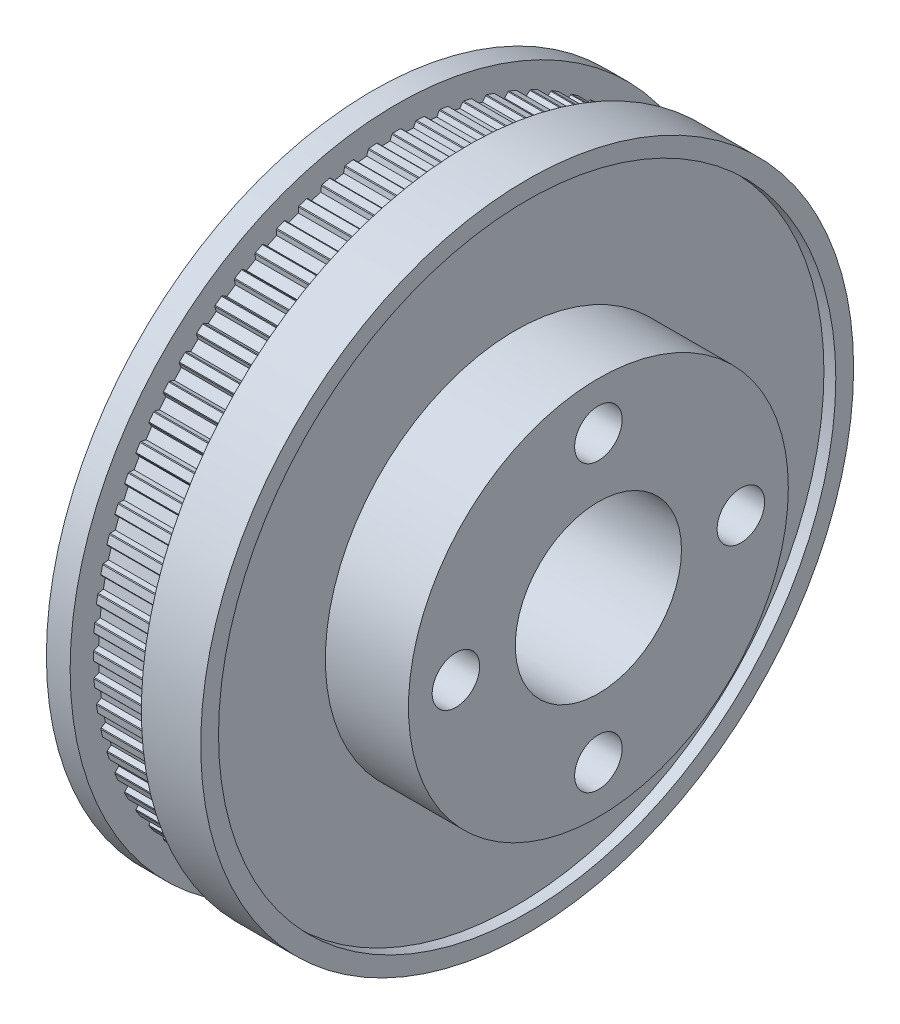
SolidWorks part; units mm, degrees
other "Câmera1"
ref_plane "Plano frontal" through (0, 0, 0) normal (0, 0, 1) x (1, 0, 0)
ref_plane "Plano superior" through (0, 0, 0) normal (0, 1, 0) x (1, 0, 0)
ref_plane "Plano direito" through (0, 0, 0) normal (1, 0, 0) x (0, 0, -1)
sketch "Esboço2" plane through (0, 0, 0) normal (1, 0, 0) x (0, 0, -1)
  line L0 (-0.3275, 25.545) -> (0.3325, 25.545)
  line L1 (-0.3949, 25.4981) -> (-0.5455, 25.0931)
  line L2 (0.3999, 25.4981) -> (0.5509, 25.0915)
  line L3 (1.6069, 25.4505) -> (1.425, 25.0585)
  line L4 (-0.3275, 25.545) -> (-0.3949, 25.4981)
  line L5 (1.425, 25.0585) -> (0.5509, 25.0915)
  line L6 (0.3325, 25.545) -> (0.3999, 25.4981)
  line L7 (1.6777, 25.4919) -> (1.6069, 25.4505)
  line L8 (1.6777, 25.4919) -> (2.3357, 25.4402)
  line L9 (2.3357, 25.4402) -> (2.3992, 25.3882)
  line L10 (2.3992, 25.3882) -> (2.5178, 24.9709)
  line L11 (3.3867, 24.8695) -> (2.5178, 24.9709)
  line L12 (3.5987, 25.246) -> (3.3867, 24.8695)
  line L13 (3.6727, 25.2817) -> (3.5987, 25.246)
  line L14 (3.6727, 25.2817) -> (4.3245, 25.1785)
  line L15 (4.3245, 25.1785) -> (4.3838, 25.1216)
  line L16 (4.3838, 25.1216) -> (4.4693, 24.6964)
  line L17 (5.3275, 24.5271) -> (4.4693, 24.6964)
  line L18 (5.5684, 24.8858) -> (5.3275, 24.5271)
  line L19 (5.6449, 24.9156) -> (5.5684, 24.8858)
  line L20 (5.6449, 24.9156) -> (6.2867, 24.7616)
  line L21 (6.2867, 24.7616) -> (6.3413, 24.7003)
  line L22 (6.3413, 24.7003) -> (6.3931, 24.2696)
  line L23 (7.2354, 24.0335) -> (6.3931, 24.2696)
  line L24 (7.5038, 24.3722) -> (7.2354, 24.0335)
  line L25 (7.5824, 24.3959) -> (7.5038, 24.3722)
  line L26 (7.5824, 24.3959) -> (8.2101, 24.192)
  line L27 (8.2101, 24.192) -> (8.2597, 24.1266)
  line L28 (8.2597, 24.1266) -> (8.2776, 23.6932)
  line L29 (9.0988, 23.3917) -> (8.2776, 23.6932)
  line L30 (9.3929, 23.7083) -> (9.0988, 23.3917)
  line L31 (9.4731, 23.7258) -> (9.3929, 23.7083)
  line L32 (9.4731, 23.7258) -> (10.0828, 23.4733)
  line L33 (10.0828, 23.4733) -> (10.1272, 23.4042)
  line L34 (10.1272, 23.4042) -> (10.111, 22.9707)
  line L35 (10.906, 22.6057) -> (10.111, 22.9707)
  line L36 (11.224, 22.8983) -> (10.906, 22.6057)
  line L37 (11.3054, 22.9094) -> (11.224, 22.8983)
  line L38 (11.3054, 22.9094) -> (11.8934, 22.6098)
  line L39 (11.8934, 22.6098) -> (11.9322, 22.5374)
  line L40 (11.9322, 22.5374) -> (11.8821, 22.1066)
  line L41 (12.646, 21.6804) -> (11.8821, 22.1066)
  line L42 (12.986, 21.9471) -> (12.646, 21.6804)
  line L43 (13.068, 21.9518) -> (12.986, 21.9471)
  line L44 (13.068, 21.9518) -> (13.6307, 21.607)
  line L45 (13.6307, 21.607) -> (13.6637, 21.5318)
  line L46 (13.6637, 21.5318) -> (13.58, 21.1062)
  line L47 (14.3081, 20.6213) -> (13.58, 21.1062)
  line L48 (14.6679, 20.8605) -> (14.3081, 20.6213)
  line L49 (14.75, 20.8588) -> (14.6679, 20.8605)
  line L50 (14.75, 20.8588) -> (15.284, 20.4709)
  line L51 (15.284, 20.4709) -> (15.311, 20.3934)
  line L52 (15.311, 20.3934) -> (15.1941, 19.9756)
  line L53 (15.8819, 19.4352) -> (15.1941, 19.9756)
  line L54 (16.2594, 19.6454) -> (15.8819, 19.4352)
  line L55 (16.3411, 19.6373) -> (16.2594, 19.6454)
  line L56 (16.3411, 19.6373) -> (16.843, 19.2086)
  line L57 (16.843, 19.2086) -> (16.8638, 19.1292)
  line L58 (16.8638, 19.1292) -> (16.7145, 18.722)
  line L59 (17.3578, 18.1292) -> (16.7145, 18.722)
  line L60 (17.7507, 18.3092) -> (17.3578, 18.1292)
  line L61 (17.8315, 18.2946) -> (17.7507, 18.3092)
  line L62 (17.8315, 18.2946) -> (18.2982, 17.8279)
  line L63 (18.2982, 17.8279) -> (18.3127, 17.7471)
  line L64 (18.3127, 17.7471) -> (18.1319, 17.3528)
  line L65 (18.7267, 16.7114) -> (18.1319, 17.3528)
  line L66 (19.1325, 16.86) -> (18.7267, 16.7114)
  line L67 (19.2119, 16.8392) -> (19.1325, 16.86)
  line L68 (19.2119, 16.8392) -> (19.6405, 16.3373)
  line L69 (19.6405, 16.3373) -> (19.6487, 16.2556)
  line L70 (19.6487, 16.2556) -> (19.4375, 15.8767)
  line L71 (19.9801, 15.1906) -> (19.4375, 15.8767)
  line L72 (20.3963, 15.3069) -> (19.9801, 15.1906)
  line L73 (20.4738, 15.2799) -> (20.3963, 15.3069)
  line L74 (20.4738, 15.2799) -> (20.8618, 14.746)
  line L75 (20.8618, 14.746) -> (20.8635, 14.6639)
  line L76 (20.8635, 14.6639) -> (20.6232, 14.3027)
  line L77 (21.1104, 13.5762) -> (20.6232, 14.3027)
  line L78 (21.5344, 13.6595) -> (21.1104, 13.5762)
  line L79 (21.6096, 13.6265) -> (21.5344, 13.6595)
  line L80 (21.6096, 13.6265) -> (21.9544, 13.0637)
  line L81 (21.9544, 13.0637) -> (21.9497, 12.9818)
  line L82 (21.9497, 12.9818) -> (21.6818, 12.6406)
  line L83 (22.1105, 11.878) -> (21.6818, 12.6406)
  line L84 (22.5397, 11.9278) -> (22.1105, 11.878)
  line L85 (22.6121, 11.889) -> (22.5397, 11.9278)
  line L86 (22.6121, 11.889) -> (22.9117, 11.3009)
  line L87 (22.9117, 11.3009) -> (22.9006, 11.2196)
  line L88 (22.9006, 11.2196) -> (22.6068, 10.9005)
  line L89 (22.9742, 10.1066) -> (22.6068, 10.9005)
  line L90 (23.4061, 10.1226) -> (22.9742, 10.1066)
  line L91 (23.4752, 10.0782) -> (23.4061, 10.1226)
  line L92 (23.4752, 10.0782) -> (23.7277, 9.4685)
  line L93 (23.7277, 9.4685) -> (23.7102, 9.3882)
  line L94 (23.7102, 9.3882) -> (23.3923, 9.0932)
  line L95 (23.6964, 8.2729) -> (23.3923, 9.0932)
  line L96 (24.1281, 8.2549) -> (23.6964, 8.2729)
  line L97 (24.1935, 8.2053) -> (24.1281, 8.2549)
  line L98 (24.1935, 8.2053) -> (24.3975, 7.5776)
  line L99 (24.3975, 7.5776) -> (24.3737, 7.499)
  line L100 (24.3737, 7.499) -> (24.0336, 7.2298)
  line L101 (24.2724, 6.3882) -> (24.0336, 7.2298)
  line L102 (24.7014, 6.3364) -> (24.2724, 6.3882)
  line L103 (24.7627, 6.2818) -> (24.7014, 6.3364)
  line L104 (24.7627, 6.2818) -> (24.9168, 5.64)
  line L105 (24.9168, 5.64) -> (24.887, 5.5636)
  line L106 (24.887, 5.5636) -> (24.5268, 5.3218)
  line L107 (24.6988, 4.4642) -> (24.5268, 5.3218)
  line L108 (25.1224, 4.3788) -> (24.6988, 4.4642)
  line L109 (25.1793, 4.3196) -> (25.1224, 4.3788)
  line L110 (25.1793, 4.3196) -> (25.2825, 3.6677)
  line L111 (25.2825, 3.6677) -> (25.2468, 3.5938)
  line L112 (25.2468, 3.5938) -> (24.8687, 3.3811)
  line L113 (24.9729, 2.5126) -> (24.8687, 3.3811)
  line L114 (25.3885, 2.3943) -> (24.9729, 2.5126)
  line L115 (25.4406, 2.3307) -> (25.3885, 2.3943)
  line L116 (25.4406, 2.3307) -> (25.4923, 1.6728)
  line L117 (25.4923, 1.6728) -> (25.4509, 1.6019)
  line L118 (25.4509, 1.6019) -> (25.0574, 1.4195)
  line L119 (25.0931, 0.5455) -> (25.0574, 1.4195)
  line L120 (25.4981, 0.3949) -> (25.0931, 0.5455)
  line L121 (25.545, 0.3275) -> (25.4981, 0.3949)
  line L122 (25.545, 0.3275) -> (25.545, -0.3325)
  line L123 (25.545, -0.3325) -> (25.4981, -0.3999)
  line L124 (25.4981, -0.3999) -> (25.0915, -0.5509)
  line L125 (25.0585, -1.425) -> (25.0915, -0.5509)
  line L126 (25.4505, -1.6069) -> (25.0585, -1.425)
  line L127 (25.4919, -1.6777) -> (25.4505, -1.6069)
  line L128 (25.4919, -1.6777) -> (25.4402, -2.3357)
  line L129 (25.4402, -2.3357) -> (25.3882, -2.3992)
  line L130 (25.3882, -2.3992) -> (24.9709, -2.5178)
  line L131 (24.8695, -3.3867) -> (24.9709, -2.5178)
  line L132 (25.246, -3.5987) -> (24.8695, -3.3867)
  line L133 (25.2817, -3.6727) -> (25.246, -3.5987)
  line L134 (25.2817, -3.6727) -> (25.1785, -4.3245)
  line L135 (25.1785, -4.3245) -> (25.1216, -4.3838)
  line L136 (25.1216, -4.3838) -> (24.6964, -4.4693)
  line L137 (24.5271, -5.3275) -> (24.6964, -4.4693)
  line L138 (24.8858, -5.5684) -> (24.5271, -5.3275)
  line L139 (24.9156, -5.6449) -> (24.8858, -5.5684)
  line L140 (24.9156, -5.6449) -> (24.7616, -6.2867)
  line L141 (24.7616, -6.2867) -> (24.7003, -6.3413)
  line L142 (24.7003, -6.3413) -> (24.2696, -6.3931)
  line L143 (24.0335, -7.2354) -> (24.2696, -6.3931)
  line L144 (24.3722, -7.5038) -> (24.0335, -7.2354)
  line L145 (24.3959, -7.5824) -> (24.3722, -7.5038)
  line L146 (24.3959, -7.5824) -> (24.192, -8.2101)
  line L147 (24.192, -8.2101) -> (24.1266, -8.2597)
  line L148 (24.1266, -8.2597) -> (23.6932, -8.2776)
  line L149 (23.3917, -9.0988) -> (23.6932, -8.2776)
  line L150 (23.7083, -9.3929) -> (23.3917, -9.0988)
  line L151 (23.7258, -9.4731) -> (23.7083, -9.3929)
  line L152 (23.7258, -9.4731) -> (23.4733, -10.0828)
  line L153 (23.4733, -10.0828) -> (23.4042, -10.1272)
  line L154 (23.4042, -10.1272) -> (22.9707, -10.111)
  line L155 (22.6057, -10.906) -> (22.9707, -10.111)
  line L156 (22.8983, -11.224) -> (22.6057, -10.906)
  line L157 (22.9094, -11.3054) -> (22.8983, -11.224)
  line L158 (22.9094, -11.3054) -> (22.6098, -11.8934)
  line L159 (22.6098, -11.8934) -> (22.5374, -11.9322)
  line L160 (22.5374, -11.9322) -> (22.1066, -11.8821)
  line L161 (21.6804, -12.646) -> (22.1066, -11.8821)
  line L162 (21.9471, -12.986) -> (21.6804, -12.646)
  line L163 (21.9518, -13.068) -> (21.9471, -12.986)
  line L164 (21.9518, -13.068) -> (21.607, -13.6307)
  line L165 (21.607, -13.6307) -> (21.5318, -13.6637)
  line L166 (21.5318, -13.6637) -> (21.1062, -13.58)
  line L167 (20.6213, -14.3081) -> (21.1062, -13.58)
  line L168 (20.8605, -14.6679) -> (20.6213, -14.3081)
  line L169 (20.8588, -14.75) -> (20.8605, -14.6679)
  line L170 (20.8588, -14.75) -> (20.4709, -15.284)
  line L171 (20.4709, -15.284) -> (20.3934, -15.311)
  line L172 (20.3934, -15.311) -> (19.9756, -15.1941)
  line L173 (19.4352, -15.8819) -> (19.9756, -15.1941)
  line L174 (19.6454, -16.2594) -> (19.4352, -15.8819)
  line L175 (19.6373, -16.3411) -> (19.6454, -16.2594)
  line L176 (19.6373, -16.3411) -> (19.2086, -16.843)
  line L177 (19.2086, -16.843) -> (19.1292, -16.8638)
  line L178 (19.1292, -16.8638) -> (18.722, -16.7145)
  line L179 (18.1292, -17.3578) -> (18.722, -16.7145)
  line L180 (18.3092, -17.7507) -> (18.1292, -17.3578)
  line L181 (18.2946, -17.8315) -> (18.3092, -17.7507)
  line L182 (18.2946, -17.8315) -> (17.8279, -18.2982)
  line L183 (17.8279, -18.2982) -> (17.7471, -18.3127)
  line L184 (17.7471, -18.3127) -> (17.3528, -18.1319)
  line L185 (16.7114, -18.7267) -> (17.3528, -18.1319)
  line L186 (16.86, -19.1325) -> (16.7114, -18.7267)
  line L187 (16.8392, -19.2119) -> (16.86, -19.1325)
  line L188 (16.8392, -19.2119) -> (16.3373, -19.6405)
  line L189 (16.3373, -19.6405) -> (16.2556, -19.6487)
  line L190 (16.2556, -19.6487) -> (15.8767, -19.4375)
  line L191 (15.1906, -19.9801) -> (15.8767, -19.4375)
  line L192 (15.3069, -20.3963) -> (15.1906, -19.9801)
  line L193 (15.2799, -20.4738) -> (15.3069, -20.3963)
  line L194 (15.2799, -20.4738) -> (14.746, -20.8618)
  line L195 (14.746, -20.8618) -> (14.6639, -20.8635)
  line L196 (14.6639, -20.8635) -> (14.3027, -20.6232)
  line L197 (13.5762, -21.1104) -> (14.3027, -20.6232)
  line L198 (13.6595, -21.5344) -> (13.5762, -21.1104)
  line L199 (13.6265, -21.6096) -> (13.6595, -21.5344)
  line L200 (13.6265, -21.6096) -> (13.0637, -21.9544)
  line L201 (13.0637, -21.9544) -> (12.9818, -21.9497)
  line L202 (12.9818, -21.9497) -> (12.6406, -21.6818)
  line L203 (11.878, -22.1105) -> (12.6406, -21.6818)
  line L204 (11.9278, -22.5397) -> (11.878, -22.1105)
  line L205 (11.889, -22.6121) -> (11.9278, -22.5397)
  line L206 (11.889, -22.6121) -> (11.3009, -22.9117)
  line L207 (11.3009, -22.9117) -> (11.2196, -22.9006)
  line L208 (11.2196, -22.9006) -> (10.9005, -22.6068)
  line L209 (10.1066, -22.9742) -> (10.9005, -22.6068)
  line L210 (10.1226, -23.4061) -> (10.1066, -22.9742)
  line L211 (10.0782, -23.4752) -> (10.1226, -23.4061)
  line L212 (10.0782, -23.4752) -> (9.4685, -23.7277)
  line L213 (9.4685, -23.7277) -> (9.3882, -23.7102)
  line L214 (9.3882, -23.7102) -> (9.0932, -23.3923)
  line L215 (8.2729, -23.6964) -> (9.0932, -23.3923)
  line L216 (8.2549, -24.1281) -> (8.2729, -23.6964)
  line L217 (8.2053, -24.1935) -> (8.2549, -24.1281)
  line L218 (8.2053, -24.1935) -> (7.5776, -24.3975)
  line L219 (7.5776, -24.3975) -> (7.499, -24.3737)
  line L220 (7.499, -24.3737) -> (7.2298, -24.0336)
  line L221 (6.3882, -24.2724) -> (7.2298, -24.0336)
  line L222 (6.3364, -24.7014) -> (6.3882, -24.2724)
  line L223 (6.2818, -24.7627) -> (6.3364, -24.7014)
  line L224 (6.2818, -24.7627) -> (5.64, -24.9168)
  line L225 (5.64, -24.9168) -> (5.5636, -24.887)
  line L226 (5.5636, -24.887) -> (5.3218, -24.5268)
  line L227 (4.4642, -24.6988) -> (5.3218, -24.5268)
  line L228 (4.3788, -25.1224) -> (4.4642, -24.6988)
  line L229 (4.3196, -25.1793) -> (4.3788, -25.1224)
  line L230 (4.3196, -25.1793) -> (3.6677, -25.2825)
  line L231 (3.6677, -25.2825) -> (3.5938, -25.2468)
  line L232 (3.5938, -25.2468) -> (3.3811, -24.8687)
  line L233 (2.5126, -24.9729) -> (3.3811, -24.8687)
  line L234 (2.3943, -25.3885) -> (2.5126, -24.9729)
  line L235 (2.3307, -25.4406) -> (2.3943, -25.3885)
  line L236 (2.3307, -25.4406) -> (1.6728, -25.4923)
  line L237 (1.6728, -25.4923) -> (1.6019, -25.4509)
  line L238 (1.6019, -25.4509) -> (1.4195, -25.0574)
  line L239 (0.5455, -25.0931) -> (1.4195, -25.0574)
  line L240 (0.3949, -25.4981) -> (0.5455, -25.0931)
  line L241 (0.3275, -25.545) -> (0.3949, -25.4981)
  line L242 (0.3275, -25.545) -> (-0.3325, -25.545)
  line L243 (-0.3325, -25.545) -> (-0.3999, -25.4981)
  line L244 (-0.3999, -25.4981) -> (-0.5509, -25.0915)
  line L245 (-1.425, -25.0585) -> (-0.5509, -25.0915)
  line L246 (-1.6069, -25.4505) -> (-1.425, -25.0585)
  line L247 (-1.6777, -25.4919) -> (-1.6069, -25.4505)
  line L248 (-1.6777, -25.4919) -> (-2.3357, -25.4402)
  line L249 (-2.3357, -25.4402) -> (-2.3992, -25.3882)
  line L250 (-2.3992, -25.3882) -> (-2.5178, -24.9709)
  line L251 (-3.3867, -24.8695) -> (-2.5178, -24.9709)
  line L252 (-3.5987, -25.246) -> (-3.3867, -24.8695)
  line L253 (-3.6727, -25.2817) -> (-3.5987, -25.246)
  line L254 (-3.6727, -25.2817) -> (-4.3245, -25.1785)
  line L255 (-4.3245, -25.1785) -> (-4.3838, -25.1216)
  line L256 (-4.3838, -25.1216) -> (-4.4693, -24.6964)
  line L257 (-5.3275, -24.5271) -> (-4.4693, -24.6964)
  line L258 (-5.5684, -24.8858) -> (-5.3275, -24.5271)
  line L259 (-5.6449, -24.9156) -> (-5.5684, -24.8858)
  line L260 (-5.6449, -24.9156) -> (-6.2867, -24.7616)
  line L261 (-6.2867, -24.7616) -> (-6.3413, -24.7003)
  line L262 (-6.3413, -24.7003) -> (-6.3931, -24.2696)
  line L263 (-7.2354, -24.0335) -> (-6.3931, -24.2696)
  line L264 (-7.5038, -24.3722) -> (-7.2354, -24.0335)
  line L265 (-7.5824, -24.3959) -> (-7.5038, -24.3722)
  line L266 (-7.5824, -24.3959) -> (-8.2101, -24.192)
  line L267 (-8.2101, -24.192) -> (-8.2597, -24.1266)
  line L268 (-8.2597, -24.1266) -> (-8.2776, -23.6932)
  line L269 (-9.0988, -23.3917) -> (-8.2776, -23.6932)
  line L270 (-9.3929, -23.7083) -> (-9.0988, -23.3917)
  line L271 (-9.4731, -23.7258) -> (-9.3929, -23.7083)
  line L272 (-9.4731, -23.7258) -> (-10.0828, -23.4733)
  line L273 (-10.0828, -23.4733) -> (-10.1272, -23.4042)
  line L274 (-10.1272, -23.4042) -> (-10.111, -22.9707)
  line L275 (-10.906, -22.6057) -> (-10.111, -22.9707)
  line L276 (-11.224, -22.8983) -> (-10.906, -22.6057)
  line L277 (-11.3054, -22.9094) -> (-11.224, -22.8983)
  line L278 (-11.3054, -22.9094) -> (-11.8934, -22.6098)
  line L279 (-11.8934, -22.6098) -> (-11.9322, -22.5374)
  line L280 (-11.9322, -22.5374) -> (-11.8821, -22.1066)
  line L281 (-12.646, -21.6804) -> (-11.8821, -22.1066)
  line L282 (-12.986, -21.9471) -> (-12.646, -21.6804)
  line L283 (-13.068, -21.9518) -> (-12.986, -21.9471)
  line L284 (-13.068, -21.9518) -> (-13.6307, -21.607)
  line L285 (-13.6307, -21.607) -> (-13.6637, -21.5318)
  line L286 (-13.6637, -21.5318) -> (-13.58, -21.1062)
  line L287 (-14.3081, -20.6213) -> (-13.58, -21.1062)
  line L288 (-14.6679, -20.8605) -> (-14.3081, -20.6213)
  line L289 (-14.75, -20.8588) -> (-14.6679, -20.8605)
  line L290 (-14.75, -20.8588) -> (-15.284, -20.4709)
  line L291 (-15.284, -20.4709) -> (-15.311, -20.3934)
  line L292 (-15.311, -20.3934) -> (-15.1941, -19.9756)
  line L293 (-15.8819, -19.4352) -> (-15.1941, -19.9756)
  line L294 (-16.2594, -19.6454) -> (-15.8819, -19.4352)
  line L295 (-16.3411, -19.6373) -> (-16.2594, -19.6454)
  line L296 (-16.3411, -19.6373) -> (-16.843, -19.2086)
  line L297 (-16.843, -19.2086) -> (-16.8638, -19.1292)
  line L298 (-16.8638, -19.1292) -> (-16.7145, -18.722)
  line L299 (-17.3578, -18.1292) -> (-16.7145, -18.722)
  line L300 (-17.7507, -18.3092) -> (-17.3578, -18.1292)
  line L301 (-17.8315, -18.2946) -> (-17.7507, -18.3092)
  line L302 (-17.8315, -18.2946) -> (-18.2982, -17.8279)
  line L303 (-18.2982, -17.8279) -> (-18.3127, -17.7471)
  line L304 (-18.3127, -17.7471) -> (-18.1319, -17.3528)
  line L305 (-18.7267, -16.7114) -> (-18.1319, -17.3528)
  line L306 (-19.1325, -16.86) -> (-18.7267, -16.7114)
  line L307 (-19.2119, -16.8392) -> (-19.1325, -16.86)
  line L308 (-19.2119, -16.8392) -> (-19.6405, -16.3373)
  line L309 (-19.6405, -16.3373) -> (-19.6487, -16.2556)
  line L310 (-19.6487, -16.2556) -> (-19.4375, -15.8767)
  line L311 (-19.9801, -15.1906) -> (-19.4375, -15.8767)
  line L312 (-20.3963, -15.3069) -> (-19.9801, -15.1906)
  line L313 (-20.4738, -15.2799) -> (-20.3963, -15.3069)
  line L314 (-20.4738, -15.2799) -> (-20.8618, -14.746)
  line L315 (-20.8618, -14.746) -> (-20.8635, -14.6639)
  line L316 (-20.8635, -14.6639) -> (-20.6232, -14.3027)
  line L317 (-21.1104, -13.5762) -> (-20.6232, -14.3027)
  line L318 (-21.5344, -13.6595) -> (-21.1104, -13.5762)
  line L319 (-21.6096, -13.6265) -> (-21.5344, -13.6595)
  line L320 (-21.6096, -13.6265) -> (-21.9544, -13.0637)
  line L321 (-21.9544, -13.0637) -> (-21.9497, -12.9818)
  line L322 (-21.9497, -12.9818) -> (-21.6818, -12.6406)
  line L323 (-22.1105, -11.878) -> (-21.6818, -12.6406)
  line L324 (-22.5397, -11.9278) -> (-22.1105, -11.878)
  line L325 (-22.6121, -11.889) -> (-22.5397, -11.9278)
  line L326 (-22.6121, -11.889) -> (-22.9117, -11.3009)
  line L327 (-22.9117, -11.3009) -> (-22.9006, -11.2196)
  line L328 (-22.9006, -11.2196) -> (-22.6068, -10.9005)
  line L329 (-22.9742, -10.1066) -> (-22.6068, -10.9005)
  line L330 (-23.4061, -10.1226) -> (-22.9742, -10.1066)
  line L331 (-23.4752, -10.0782) -> (-23.4061, -10.1226)
  line L332 (-23.4752, -10.0782) -> (-23.7277, -9.4685)
  line L333 (-23.7277, -9.4685) -> (-23.7102, -9.3882)
  line L334 (-23.7102, -9.3882) -> (-23.3923, -9.0932)
  line L335 (-23.6964, -8.2729) -> (-23.3923, -9.0932)
  line L336 (-24.1281, -8.2549) -> (-23.6964, -8.2729)
  line L337 (-24.1935, -8.2053) -> (-24.1281, -8.2549)
  line L338 (-24.1935, -8.2053) -> (-24.3975, -7.5776)
  line L339 (-24.3975, -7.5776) -> (-24.3737, -7.499)
  line L340 (-24.3737, -7.499) -> (-24.0336, -7.2298)
  line L341 (-24.2724, -6.3882) -> (-24.0336, -7.2298)
  line L342 (-24.7014, -6.3364) -> (-24.2724, -6.3882)
  line L343 (-24.7627, -6.2818) -> (-24.7014, -6.3364)
  line L344 (-24.7627, -6.2818) -> (-24.9168, -5.64)
  line L345 (-24.9168, -5.64) -> (-24.887, -5.5636)
  line L346 (-24.887, -5.5636) -> (-24.5268, -5.3218)
  line L347 (-24.6988, -4.4642) -> (-24.5268, -5.3218)
  line L348 (-25.1224, -4.3788) -> (-24.6988, -4.4642)
  line L349 (-25.1793, -4.3196) -> (-25.1224, -4.3788)
  line L350 (-25.1793, -4.3196) -> (-25.2825, -3.6677)
  line L351 (-25.2825, -3.6677) -> (-25.2468, -3.5938)
  line L352 (-25.2468, -3.5938) -> (-24.8687, -3.3811)
  line L353 (-24.9729, -2.5126) -> (-24.8687, -3.3811)
  line L354 (-25.3885, -2.3943) -> (-24.9729, -2.5126)
  line L355 (-25.4406, -2.3307) -> (-25.3885, -2.3943)
  line L356 (-25.4406, -2.3307) -> (-25.4923, -1.6728)
  line L357 (-25.4923, -1.6728) -> (-25.4509, -1.6019)
  line L358 (-25.4509, -1.6019) -> (-25.0574, -1.4195)
  line L359 (-25.0931, -0.5455) -> (-25.0574, -1.4195)
  line L360 (-25.4981, -0.3949) -> (-25.0931, -0.5455)
  line L361 (-25.545, -0.3275) -> (-25.4981, -0.3949)
  line L362 (-25.545, -0.3275) -> (-25.545, 0.3325)
  line L363 (-25.545, 0.3325) -> (-25.4981, 0.3999)
  line L364 (-25.4981, 0.3999) -> (-25.0915, 0.5509)
  line L365 (-25.0585, 1.425) -> (-25.0915, 0.5509)
  line L366 (-25.4505, 1.6069) -> (-25.0585, 1.425)
  line L367 (-25.4919, 1.6777) -> (-25.4505, 1.6069)
  line L368 (-25.4919, 1.6777) -> (-25.4402, 2.3357)
  line L369 (-25.4402, 2.3357) -> (-25.3882, 2.3992)
  line L370 (-25.3882, 2.3992) -> (-24.9709, 2.5178)
  line L371 (-24.8695, 3.3867) -> (-24.9709, 2.5178)
  line L372 (-25.246, 3.5987) -> (-24.8695, 3.3867)
  line L373 (-25.2817, 3.6727) -> (-25.246, 3.5987)
  line L374 (-25.2817, 3.6727) -> (-25.1785, 4.3245)
  line L375 (-25.1785, 4.3245) -> (-25.1216, 4.3838)
  line L376 (-25.1216, 4.3838) -> (-24.6964, 4.4693)
  line L377 (-24.5271, 5.3275) -> (-24.6964, 4.4693)
  line L378 (-24.8858, 5.5684) -> (-24.5271, 5.3275)
  line L379 (-24.9156, 5.6449) -> (-24.8858, 5.5684)
  line L380 (-24.9156, 5.6449) -> (-24.7616, 6.2867)
  line L381 (-24.7616, 6.2867) -> (-24.7003, 6.3413)
  line L382 (-24.7003, 6.3413) -> (-24.2696, 6.3931)
  line L383 (-24.0335, 7.2354) -> (-24.2696, 6.3931)
  line L384 (-24.3722, 7.5038) -> (-24.0335, 7.2354)
  line L385 (-24.3959, 7.5824) -> (-24.3722, 7.5038)
  line L386 (-24.3959, 7.5824) -> (-24.192, 8.2101)
  line L387 (-24.192, 8.2101) -> (-24.1266, 8.2597)
  line L388 (-24.1266, 8.2597) -> (-23.6932, 8.2776)
  line L389 (-23.3917, 9.0988) -> (-23.6932, 8.2776)
  line L390 (-23.7083, 9.3929) -> (-23.3917, 9.0988)
  line L391 (-23.7258, 9.4731) -> (-23.7083, 9.3929)
  line L392 (-23.7258, 9.4731) -> (-23.4733, 10.0828)
  line L393 (-23.4733, 10.0828) -> (-23.4042, 10.1272)
  line L394 (-23.4042, 10.1272) -> (-22.9707, 10.111)
  line L395 (-22.6057, 10.906) -> (-22.9707, 10.111)
  line L396 (-22.8983, 11.224) -> (-22.6057, 10.906)
  line L397 (-22.9094, 11.3054) -> (-22.8983, 11.224)
  line L398 (-22.9094, 11.3054) -> (-22.6098, 11.8934)
  line L399 (-22.6098, 11.8934) -> (-22.5374, 11.9322)
  line L400 (-22.5374, 11.9322) -> (-22.1066, 11.8821)
  line L401 (-21.6804, 12.646) -> (-22.1066, 11.8821)
  line L402 (-21.9471, 12.986) -> (-21.6804, 12.646)
  line L403 (-21.9518, 13.068) -> (-21.9471, 12.986)
  line L404 (-21.9518, 13.068) -> (-21.607, 13.6307)
  line L405 (-21.607, 13.6307) -> (-21.5318, 13.6637)
  line L406 (-21.5318, 13.6637) -> (-21.1062, 13.58)
  line L407 (-20.6213, 14.3081) -> (-21.1062, 13.58)
  line L408 (-20.8605, 14.6679) -> (-20.6213, 14.3081)
  line L409 (-20.8588, 14.75) -> (-20.8605, 14.6679)
  line L410 (-20.8588, 14.75) -> (-20.4709, 15.284)
  line L411 (-20.4709, 15.284) -> (-20.3934, 15.311)
  line L412 (-20.3934, 15.311) -> (-19.9756, 15.1941)
  line L413 (-19.4352, 15.8819) -> (-19.9756, 15.1941)
  line L414 (-19.6454, 16.2594) -> (-19.4352, 15.8819)
  line L415 (-19.6373, 16.3411) -> (-19.6454, 16.2594)
  line L416 (-19.6373, 16.3411) -> (-19.2086, 16.843)
  line L417 (-19.2086, 16.843) -> (-19.1292, 16.8638)
  line L418 (-19.1292, 16.8638) -> (-18.722, 16.7145)
  line L419 (-18.1292, 17.3578) -> (-18.722, 16.7145)
  line L420 (-18.3092, 17.7507) -> (-18.1292, 17.3578)
  line L421 (-18.2946, 17.8315) -> (-18.3092, 17.7507)
  line L422 (-18.2946, 17.8315) -> (-17.8279, 18.2982)
  line L423 (-17.8279, 18.2982) -> (-17.7471, 18.3127)
  line L424 (-17.7471, 18.3127) -> (-17.3528, 18.1319)
  line L425 (-16.7114, 18.7267) -> (-17.3528, 18.1319)
  line L426 (-16.86, 19.1325) -> (-16.7114, 18.7267)
  line L427 (-16.8392, 19.2119) -> (-16.86, 19.1325)
  line L428 (-16.8392, 19.2119) -> (-16.3373, 19.6405)
  line L429 (-16.3373, 19.6405) -> (-16.2556, 19.6487)
  line L430 (-16.2556, 19.6487) -> (-15.8767, 19.4375)
  line L431 (-15.1906, 19.9801) -> (-15.8767, 19.4375)
  line L432 (-15.3069, 20.3963) -> (-15.1906, 19.9801)
  line L433 (-15.2799, 20.4738) -> (-15.3069, 20.3963)
  line L434 (-15.2799, 20.4738) -> (-14.746, 20.8618)
  line L435 (-14.746, 20.8618) -> (-14.6639, 20.8635)
  line L436 (-14.6639, 20.8635) -> (-14.3027, 20.6232)
  line L437 (-13.5762, 21.1104) -> (-14.3027, 20.6232)
  line L438 (-13.6595, 21.5344) -> (-13.5762, 21.1104)
  line L439 (-13.6265, 21.6096) -> (-13.6595, 21.5344)
  line L440 (-13.6265, 21.6096) -> (-13.0637, 21.9544)
  line L441 (-13.0637, 21.9544) -> (-12.9818, 21.9497)
  line L442 (-12.9818, 21.9497) -> (-12.6406, 21.6818)
  line L443 (-11.878, 22.1105) -> (-12.6406, 21.6818)
  line L444 (-11.9278, 22.5397) -> (-11.878, 22.1105)
  line L445 (-11.889, 22.6121) -> (-11.9278, 22.5397)
  line L446 (-11.889, 22.6121) -> (-11.3009, 22.9117)
  line L447 (-11.3009, 22.9117) -> (-11.2196, 22.9006)
  line L448 (-11.2196, 22.9006) -> (-10.9005, 22.6068)
  line L449 (-10.1066, 22.9742) -> (-10.9005, 22.6068)
  line L450 (-10.1226, 23.4061) -> (-10.1066, 22.9742)
  line L451 (-10.0782, 23.4752) -> (-10.1226, 23.4061)
  line L452 (-10.0782, 23.4752) -> (-9.4685, 23.7277)
  line L453 (-9.4685, 23.7277) -> (-9.3882, 23.7102)
  line L454 (-9.3882, 23.7102) -> (-9.0932, 23.3923)
  line L455 (-8.2729, 23.6964) -> (-9.0932, 23.3923)
  line L456 (-8.2549, 24.1281) -> (-8.2729, 23.6964)
  line L457 (-8.2053, 24.1935) -> (-8.2549, 24.1281)
  line L458 (-8.2053, 24.1935) -> (-7.5776, 24.3975)
  line L459 (-7.5776, 24.3975) -> (-7.499, 24.3737)
  line L460 (-7.499, 24.3737) -> (-7.2298, 24.0336)
  line L461 (-6.3882, 24.2724) -> (-7.2298, 24.0336)
  line L462 (-6.3364, 24.7014) -> (-6.3882, 24.2724)
  line L463 (-6.2818, 24.7627) -> (-6.3364, 24.7014)
  line L464 (-6.2818, 24.7627) -> (-5.64, 24.9168)
  line L465 (-5.64, 24.9168) -> (-5.5636, 24.887)
  line L466 (-5.5636, 24.887) -> (-5.3218, 24.5268)
  line L467 (-4.4642, 24.6988) -> (-5.3218, 24.5268)
  line L468 (-4.3788, 25.1224) -> (-4.4642, 24.6988)
  line L469 (-4.3196, 25.1793) -> (-4.3788, 25.1224)
  line L470 (-4.3196, 25.1793) -> (-3.6677, 25.2825)
  line L471 (-3.6677, 25.2825) -> (-3.5938, 25.2468)
  line L472 (-3.5938, 25.2468) -> (-3.3811, 24.8687)
  line L473 (-2.5126, 24.9729) -> (-3.3811, 24.8687)
  line L474 (-2.3943, 25.3885) -> (-2.5126, 24.9729)
  line L475 (-2.3307, 25.4406) -> (-2.3943, 25.3885)
  line L476 (-2.3307, 25.4406) -> (-1.6728, 25.4923)
  line L477 (-1.6728, 25.4923) -> (-1.6019, 25.4509)
  line L478 (-1.6019, 25.4509) -> (-1.4195, 25.0574)
  line L479 (-0.5455, 25.0931) -> (-1.4195, 25.0574)
  arc A0 (0.3357, 25.5428) -> (-0.3306, 25.5429) centre (0, 0) ccw
  point P1 (0.3825, 25.545)
  point P2 (-0.3775, 25.545)
  point P15 (1.425, 25.0585)
  point P569 (0, 0)
  dimension "D2" = 80
  dimension "D1" = 0.76
extrude "Ressalto-extrusão1" add sketch "Esboço2" along normal blind 6 contours L6 A0 L4 L1 L479 L478 L477 L476 L475 L474 L473 L472 L471 L470 L469 L468 L467 L466 L465 L464 L463 L462 L461 L460 L459 L458 L457 L456 L455 L454 L453 L452 L451 L450 L449 L448 L447 L446 L445 L444 L443 L442 L441 L440 L439 L438 L437 L436 L435 L434 region at (0, 0, 0)
ref_plane "Plano1" through (-12.7, 0, 0) normal (0, -1, 0) x (0, 0, -1)
sketch "Sketch1" plane through (0, 0, 0) normal (-1, 0, 0) x (0, 0, 1)
  circle A0 centre (0, 0) radius 27.5
  dimension "D1" = 55
extrude "Boss-Extrude1" add sketch "Sketch1" along normal blind 2
sketch "Sketch2" plane through (6, 0, 0) normal (1, 0, 0) x (0, 0, -1)
  circle A0 centre (0, 0) radius 27.5
  dimension "D1" = 55
extrude "Boss-Extrude2" add sketch "Sketch2" along normal blind 5
sketch "Sketch3" plane through (11, 0, 0) normal (1, 0, 0) x (0, 0, -1)
  circle A0 centre (0, 0) radius 26
  dimension "D1" = 52
extrude "Cut-Extrude4" cut sketch "Sketch3" against normal blind 1
sketch "Sketch7" plane through (10, 0, 0) normal (1, 0, 0) x (0, 0, -1)
  circle A0 centre (0, 0) radius 16
  dimension "D1" = 32
extrude "Boss-Extrude4" add sketch "Sketch7" along normal blind 7
sketch "Sketch5" plane through (11, 0, 0) normal (1, 0, 0) x (0, 0, -1)
  circle A0 centre (0, 12) radius 2
  point P2 (0, 0)
  point P4 (0, 0)
  dimension "D1" = 4
  dimension "D2" = 12
extrude "Cut-Extrude2" cut sketch "Sketch5" against normal through all and the other way through all
pattern_circular "CirPattern1" count 4 over 360 about axis through (11, 0, 0) along (1, 0, 0) of "Cut-Extrude2"
sketch "Sketch8" plane through (17, 0, 0) normal (1, 0, 0) x (0, 0, -1)
  circle A0 centre (0, 0) radius 7
  dimension "D1" = 14
extrude "Cut-Extrude5" cut sketch "Sketch8" against normal through all
